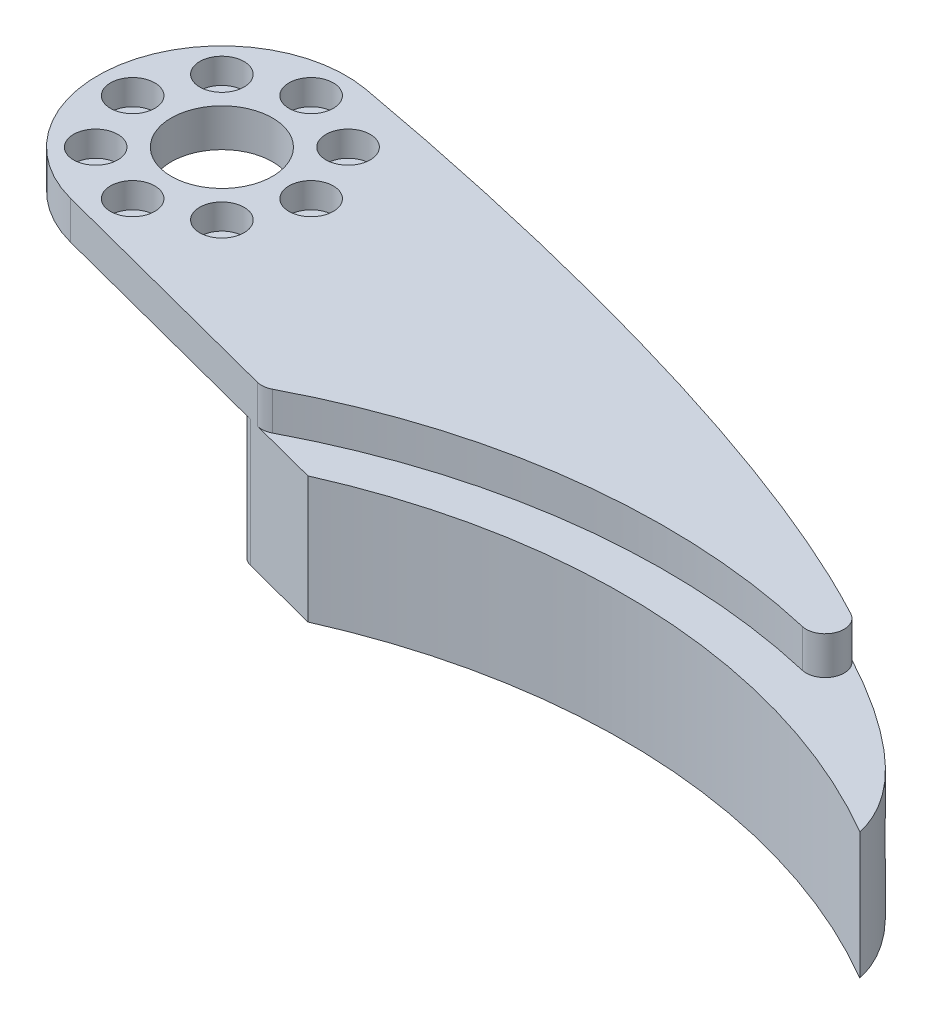
SolidWorks part; units mm, degrees
ref_plane "Front Plane" through (0, 0, 0) normal (0, 0, 1) x (1, 0, 0)
ref_plane "Top Plane" through (0, 0, 0) normal (0, 1, 0) x (1, 0, 0)
ref_plane "Right Plane" through (0, 0, 0) normal (1, 0, 0) x (0, 0, -1)
sketch "Sketch1" plane through (0, 0, 0) normal (0, 1, 0) x (1, 0, 0)
  line L2 (22.89, -16.09) -> (-2.4705, -9.4835)
  arc A3 (22.89, -16.09) -> (69.042, -18.6456) centre (43.4752, -62.3492) cw
  arc A4 (1.753, 9.6419) -> (-2.4705, -9.4835) centre (0, 0) ccw
  arc A5 (18.0515, -14.8295) -> (65.6466, -13.2278) centre (43.4752, -62.3492) cw
  arc A6 (13.213, -13.5691) -> (54.8271, -6.0781) centre (43.4752, -62.3492) cw
  circle A7 centre (0, 7.05) radius 1
  circle A8 centre (4.9851, 4.9851) radius 1
  circle A9 centre (7.05, 0) radius 1
  circle A10 centre (4.9851, -4.9851) radius 1
  circle A11 centre (0, -7.05) radius 1
  circle A12 centre (-4.9851, -4.9851) radius 1
  circle A13 centre (-7.05, 0) radius 1
  circle A14 centre (-4.9851, 4.9851) radius 1
  circle A15 centre (0, 0) radius 4
  spline S0 degree 3 poles (1.753, 9.6419) (36.783, 3.273) (66.7324, -7.9212) (69.042, -18.6456) knots 0 0 0 0 1 1 1 1
  point P5 (0, 0)
  point P32 (0, 0)
  dimension "D1" = 5
  dimension "D2" = 50.6327
  dimension "D4" = 19.6
  dimension "D8" = 76.01
  dimension "D3" = 5
  dimension "D9" = 7.05
  dimension "D10" = 2
  dimension "D12" = 8
  dimension "D6" = 16.09
  dimension "D7" = 22.89
  dimension "D5" = 48
  dimension "D11" = 8
extrude "Boss-Extrude1" add sketch "Sketch1" along normal blind 3 contours S0 A4 L2 A6 A14 A13 A12 A11 A10 A9 A8 A7 | S0 A6 L2 A5 region at (37.8967, 0, 8.7061) region at (14.7487, 0, 1.7674)
extrude "Boss-Extrude2" add sketch "Sketch1<3>" against normal blind 10 contours S0 A5 L2 A3 | S0 A6 L2 A5 region at (20.6018, 0, 14.9566) region at (37.8967, 0, 8.7061)
sketch "Sketch1<3>" plane through (0, 0, 0) normal (0, 1, 0) x (1, 0, 0) same geometry as "Sketch1"
sketch "Sketch2" plane through (0, 3, 0) normal (0, 1, 0) x (1, 0, 0)
  circle A0 centre (0, 7.05) radius 1.75
  circle A1 centre (4.9851, 4.9851) radius 1.75
  circle A2 centre (7.05, 0) radius 1.75
  circle A3 centre (4.9851, -4.9851) radius 1.75
  circle A4 centre (0, -7.05) radius 1.75
  circle A5 centre (-4.9851, -4.9851) radius 1.75
  circle A6 centre (-7.05, 0) radius 1.75
  circle A7 centre (-4.9851, 4.9851) radius 1.75
  point P19 (0, 0)
  dimension "D1" = 3.5
  dimension "D2" = 8
extrude "Cut-Extrude1" cut sketch "Sketch2" against normal offset from surface (2 mm away) 1 up to face at (7.715, 0, 1.4059)
fillet "Fillet1" radius 1.5 4 edges at (54.8271, -5, 6.0781) (13.213, -5, 13.5691) (18.0515, 1.5, 14.8295) (65.6466, 1.5, 13.2278)
